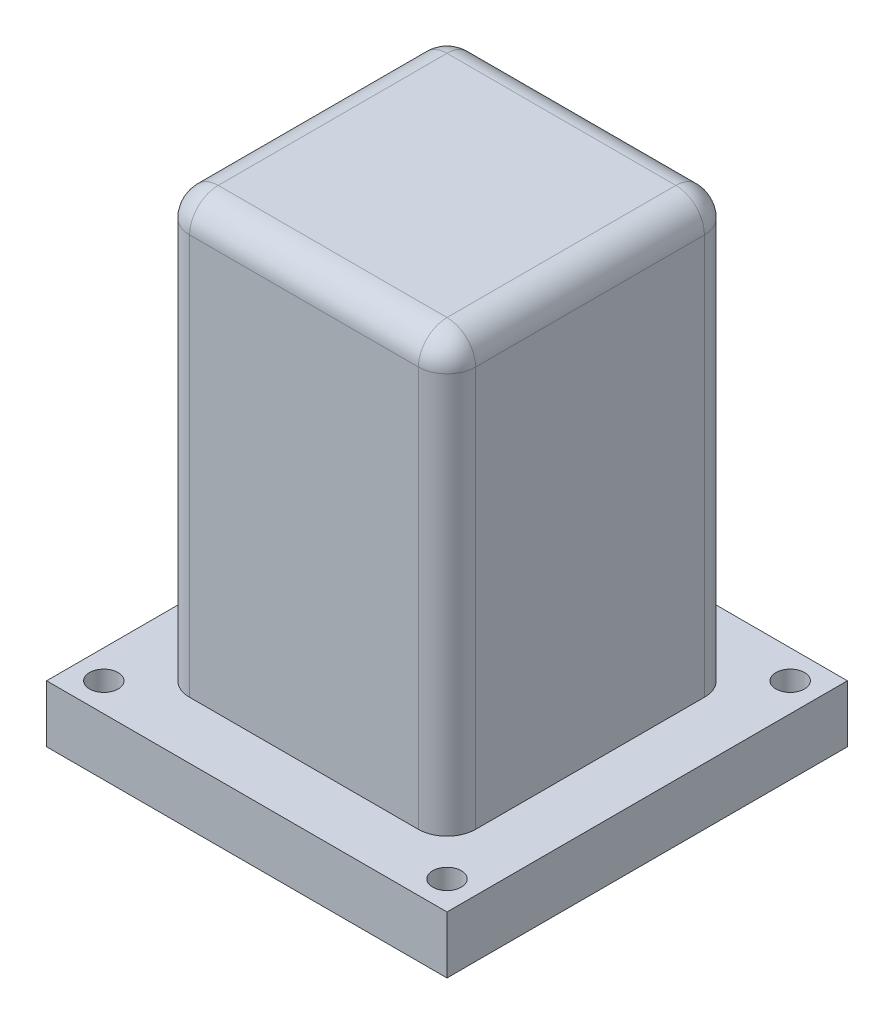
SolidWorks part; units mm, degrees
ref_plane "Front Plane" through (0, 0, 0) normal (0, 0, 1) x (1, 0, 0)
ref_plane "Top Plane" through (0, 0, 0) normal (0, 1, 0) x (1, 0, 0)
ref_plane "Right Plane" through (0, 0, 0) normal (1, 0, 0) x (0, 0, -1)
sketch "Sketch1" plane through (0, 0, 0) normal (0, 1, 0) x (1, 0, 0)
  line L1 (-25, 25) -> (25, 25)
  line L2 (-25, 25) -> (-25, -25)
  line L3 (-25, -25) -> (25, -25)
  line L4 (25, 25) -> (25, -25)
  line L5 (-25, 25) -> (25, -25) construction
  line L6 (-25, -25) -> (25, 25) construction
  point P1 (0, 0)
  dimension "D1" = 50
  dimension "D2" = 50
extrude "Boss-Extrude1" add sketch "Sketch1" along normal blind 85
sketch "Sketch2" plane through (0, 0, 0) normal (0, -1, 0) x (1, 0, 0)
  circle A0 centre (0, 0) radius 5
  dimension "D1" = 10
extrude "Boss-Extrude2" add sketch "Sketch2" along normal blind 30
fillet "Fillet1" radius 5 4 edges at (0, 0, 25) (0, 85, 25) (25, 42.5, 25) (-25, 42.5, 25)
fillet "Fillet2" radius 5 8 edges at (-23.5355, 83.5355, 23.5355) (23.5355, 83.5355, 23.5355) (-23.5355, 1.4645, 23.5355) (23.5355, 1.4645, 23.5355) (-25, 85, -2.5) (25, 85, -2.5) (-25, 0, -2.5) (25, 0, -2.5)
sketch "Sketch3" plane through (0, 0, 0) normal (0, -1, 0) x (1, 0, 0)
  line L1 (-35, 35) -> (35, 35)
  line L2 (-35, 35) -> (-35, -35)
  line L3 (-35, -35) -> (35, -35)
  line L4 (35, 35) -> (35, -35)
  line L5 (-35, 35) -> (35, -35) construction
  line L6 (-35, -35) -> (35, 35) construction
  point P0 (0, 0)
  dimension "D1" = 70
  dimension "D2" = 70
extrude "Boss-Extrude3" add sketch "Sketch3" against normal blind 10
fillet "Fillet3" radius 5 5 edges at (-25, 45, -25) (-23.5355, 83.5355, -25) (0, 85, -25) (23.5355, 83.5355, -25) (25, 45, -25)
sketch "Sketch4" plane through (0, 0, 0) normal (0, -1, 0) x (1, 0, 0)
  line L0 (35, 35) -> (-35, 35) construction
  line L1 (-35, 35) -> (-35, -35) construction
  circle A0 centre (-30, 30) radius 2.5
  circle A1 centre (30, 30) radius 2.5
  circle A2 centre (30, -30) radius 2.5
  circle A3 centre (-30, -30) radius 2.5
  point P15 (0, 0)
  dimension "D1" = 5
  dimension "D2" = 5
  dimension "D3" = 5
  dimension "D4" = 4
extrude "Cut-Extrude1" cut sketch "Sketch4" against normal blind 10
